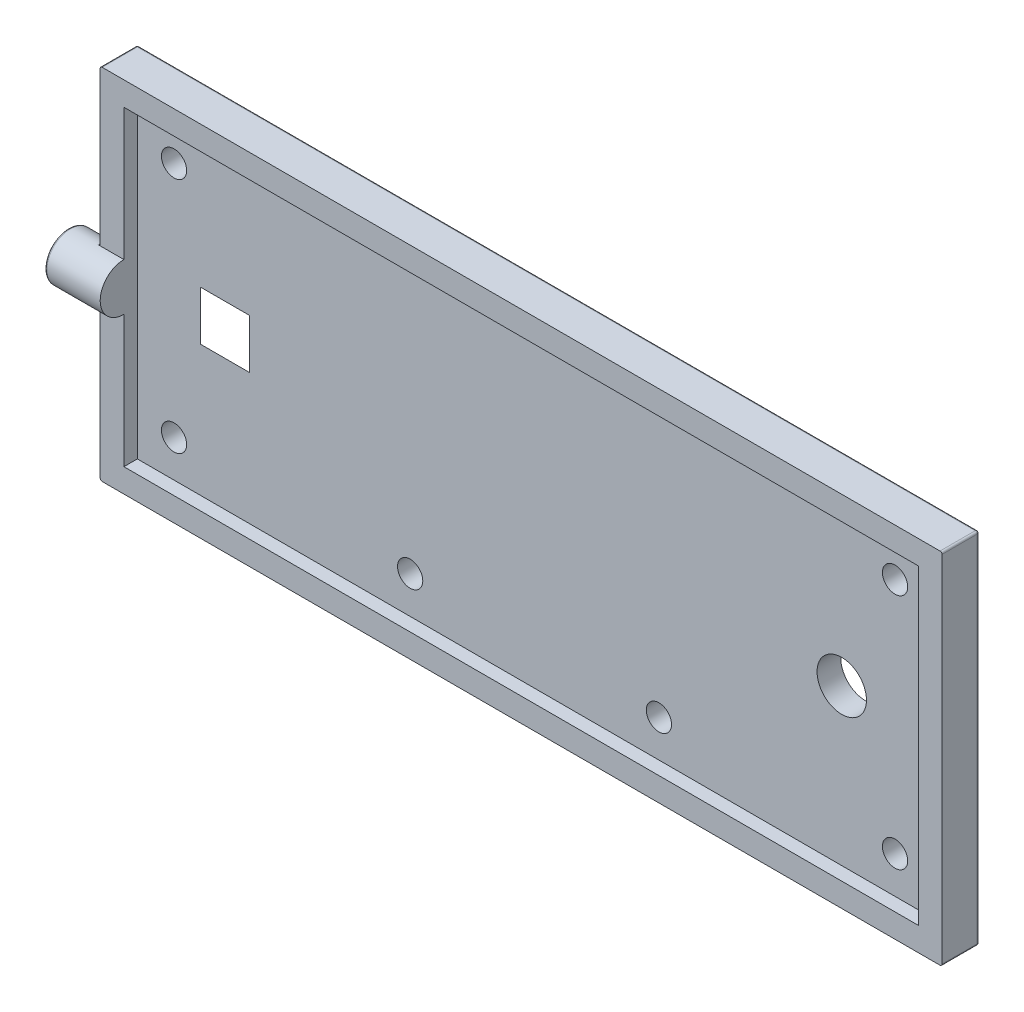
SolidWorks part; units mm, degrees
ref_plane "Front Plane" through (0, 0, 0) normal (0, 0, 1) x (1, 0, 0)
ref_plane "Top Plane" through (0, 0, 0) normal (0, 1, 0) x (1, 0, 0)
ref_plane "Right Plane" through (0, 0, 0) normal (1, 0, 0) x (0, 0, -1)
sketch "Sketch1" plane through (0, 0, 0) normal (0, 0, 1) x (1, 0, 0)
  line L0 (92.08, 42.37) -> (92.08, 3) construction
  line L1 (0, 0) -> (106.46, 0)
  line L2 (0, 0) -> (0, 45.37)
  line L3 (0, 45.37) -> (106.46, 45.37)
  line L4 (106.46, 0) -> (106.46, 45.37)
  line L5 (3, 3) -> (103.46, 3)
  line L6 (3, 3) -> (3, 42.37)
  line L7 (3, 42.37) -> (103.46, 42.37)
  line L8 (103.46, 3) -> (103.46, 42.37)
  line L10 (10.955, 25.81) -> (17.205, 25.81)
  line L11 (10.955, 25.81) -> (10.955, 19.56)
  line L12 (10.955, 19.56) -> (17.205, 19.56)
  line L13 (17.205, 25.81) -> (17.205, 19.56)
  line L14 (10.955, 25.81) -> (17.205, 19.56) construction
  line L15 (10.955, 19.56) -> (17.205, 25.81) construction
  circle A0 centre (7.64, 7.68) radius 1.595
  circle A1 centre (37.5, 7.68) radius 1.595
  circle A2 centre (68.96, 7.68) radius 1.595
  circle A3 centre (98.82, 7.68) radius 1.595
  circle A4 centre (7.64, 37.69) radius 1.595
  circle A5 centre (98.82, 37.69) radius 1.595
  circle A6 centre (92.08, 22.685) radius 3.125
  point P25 (14.08, 22.685)
  dimension "D7" = 3.19
  dimension "D8" = 3.19
  dimension "D9" = 3.19
  dimension "D10" = 3.19
  dimension "D11" = 3.19
  dimension "D14" = 3.19
  dimension "D19" = 6.25
  dimension "D1" = 45.37
  dimension "D2" = 106.46
  dimension "D3" = 3
  dimension "D4" = 3
  dimension "D5" = 3
  dimension "D6" = 3
  dimension "D12" = 4.68
  dimension "D13" = 4.64
  dimension "D15" = 4.68
  dimension "D16" = 29.86
  dimension "D17" = 31.46
  dimension "D18" = 29.86
  dimension "D20" = 11.38
  dimension "D21" = 78
  dimension "D22" = 6.25
extrude "Boss-Extrude1" add sketch "Sketch1" along normal blind 3 contours L0 L7 L6 L5 A6 A4 A2 A1 A0 | L7 L0 A6 L5 L8 A3 A5 region at (53.3179, 22.7475, 0)
extrude "Boss-Extrude2" add sketch "Sketch1<5>" along normal blind 4.7 contours L1 L4 L3 L2 L8 L5 L6 L7 region at (1.1572, 22.685, 0)
sketch "Sketch1<5>" plane through (0, 0, 0) normal (0, 0, 1) x (1, 0, 0) same geometry as "Sketch1"
sketch "Sketch2" plane through (0, 0, 0) normal (-1, 0, 0) x (0, 0, 1)
  line L0 (4.7, 0) -> (4.7, 45.37) construction
  circle A0 centre (4.7, 22.685) radius 3
extrude "Boss-Extrude3" add sketch "Sketch2" along normal blind 4 and the other way blind 3
fillet "Fillet1" radius 0.25 10 edges at (-4, 22.685, 7.7) (0, 45.37, 2.35) (53.23, 45.37, 0) (106.46, 45.37, 2.35) (106.46, 0, 2.35) (106.46, 22.685, 0) (0, 0, 2.35) (53.23, 0, 0) (0, 22.685, 0) (0, 22.685, 1.7)
chamfer "Chamfer1" distance 3 angle 70 4 edges at (10.955, 22.685, 0) (14.08, 25.81, 0) (17.205, 22.685, 0) (14.08, 19.56, 0) first distance on face at (10.955, 22.685, 1.5) first distance on face at (14.08, 25.81, 1.5) first distance on face at (17.205, 22.685, 1.5) first distance on face at (14.08, 19.56, 1.5)
